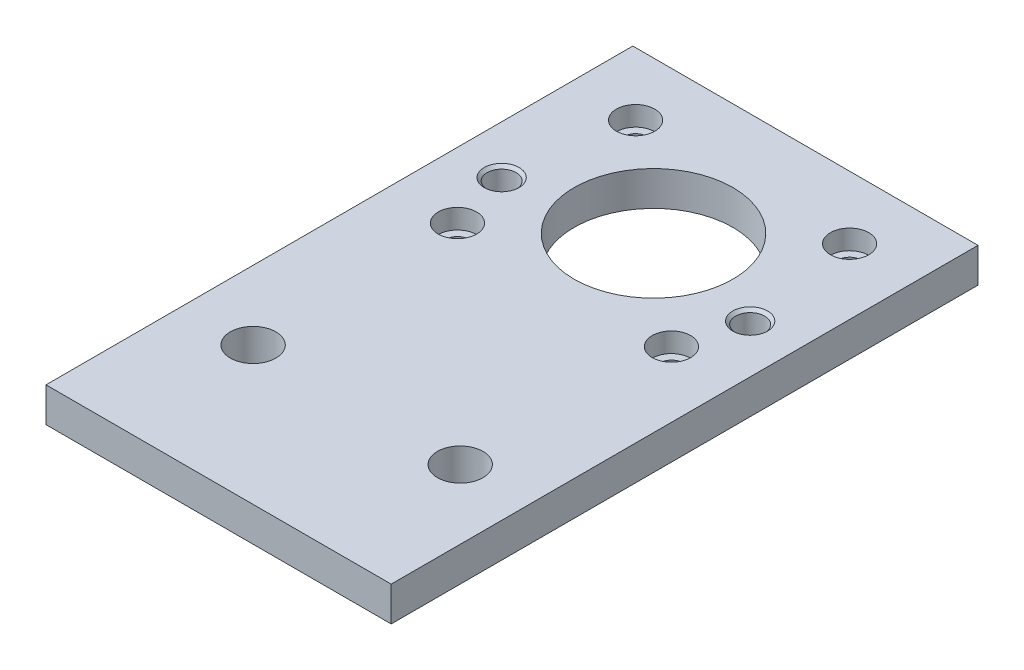
SolidWorks part; units mm, degrees
material "6061-T6 (SS)"
ref_plane "Front Plane" through (0, 0, 0) normal (0, 0, 1) x (1, 0, 0)
ref_plane "Top Plane" through (0, 0, 0) normal (0, 1, 0) x (1, 0, 0)
ref_plane "Right Plane" through (0, 0, 0) normal (1, 0, 0) x (0, 0, -1)
sketch "Sketch1" plane through (0, 0, 0) normal (0, 1, 0) x (1, 0, 0)
  line L0 (5.9071, 63) -> (47.5761, 63) construction
  line L1 (0, 0) -> (50, 0)
  line L2 (0, 0) -> (0, 85)
  line L3 (0, 85) -> (50, 85)
  line L4 (50, 0) -> (50, 85)
  circle A0 centre (25, 63) radius 11.5
  point P7 (25, 85)
  dimension "D4" = 23
  dimension "D1" = 50
  dimension "D2" = 85
  dimension "D3" = 22
extrude "Boss-Extrude1" add sketch "Sketch1" along normal blind 5
hole_wizard "CBORE for #4 Socket Head Cap Screw1" positions "Sketch3" profile "Sketch4" counterbore size "#4" standard "Ansi Inch" end condition through all
sketch "Sketch3" plane through (0, 5, 0) normal (0, 1, 0) x (-1, 0, 0)
  line L7 (-3.7215, -63) -> (-48.1912, -63) construction
  line L9 (-25, -48.4116) -> (-25, -77.5767) construction
  point P0 (-9.5, -75.9033)
  point P76 (-9.5, -50.0967)
  point P78 (-40.5, -50.0967)
  point P79 (-40.5, -75.9033)
  dimension "D1" = 31
sketch "Sketch4" plane through (9.5, 5, -75.9033) normal (1, 0, 0) x (0, 0, 1)
  line L0 (0, 0) -> (0, 5)
  line L1 (0, 5) -> (1.6319, 5)
  line L3 (1.6319, 5) -> (1.6319, 2.8448)
  line L4 (1.6319, 2.8448) -> (2.7788, 2.8448)
  line L5 (2.7788, 2.8448) -> (2.7788, 0)
  line L7 (2.7788, 0) -> (0, 0)
  line L11 (0, -6.35) -> (0, 107.95) construction
  dimension "Thru Hole Dia." = 3.2639
  dimension "Thru Hole Depth" = 5
  dimension "C'Bore Dia." = 5.5575
  dimension "C'Bore Depth" = 2.8448
hole_wizard "M6 Clearance Hole1" positions "Sketch6" profile "Sketch5" hole size "M6" standard "ISO" end condition up to next
sketch "Sketch6" plane through (0, 5, 0) normal (0, 1, 0) x (-1, 0, 0)
  line L0 (-25, 0) -> (-25, -85) construction
  line L1 (0, 0) -> (-50, 0) construction
  line L2 (-50, -85) -> (0, -85) construction
  point P0 (-10, -20)
  point P13 (-40, -20)
  dimension "D1" = 30
  dimension "D2" = 20
sketch "Sketch5" plane through (10, 5, -20) normal (1, 0, 0) x (0, 0, 1)
  line L0 (0, 0) -> (0, 5)
  line L1 (0, 5) -> (3.3, 5)
  line L2 (3.3, 5) -> (3.3, 0)
  line L5 (3.3, 0) -> (0, 0)
  line L11 (0, -6.35) -> (0, 107.95) construction
  dimension "Thru Hole Dia." = 6.6
  dimension "Thru Hole Depth" = 5
ref_axis "Axis1" through (25, 5, -63) along (0, -1, 0)
hole_wizard "M5 Tapped Hole1" positions "Sketch8" profile "Sketch7" tap size "M5" standard "ISO" end condition up to next
sketch "Sketch8" plane through (0, 5, 0) normal (0, 1, 0) x (-1, 0, 0)
  line L0 (-25, -76.9089) -> (-25, -49.0911) construction
  point P0 (-7, -59)
  point P17 (-43, -59)
  dimension "D1" = 18
  dimension "D2" = 4
sketch "Sketch7" plane through (7, 5, -59) normal (1, 0, 0) x (0, 0, 1)
  line L0 (0, 0) -> (0, 5)
  line L1 (0, 5) -> (2.1, 5)
  line L2 (2.1, 5) -> (2.1, 0.425)
  line L3 (2.1, 0.425) -> (2.525, 0)
  line L5 (2.525, 0) -> (0, 0)
  line L6 (-2.1, 0.425) -> (-2.525, 0) construction
  line L11 (0, -6.35) -> (0, 107.95) construction
  dimension "Thru Tap Drill Dia." = 4.2
  dimension "Thru Tap Drill Depth" = 5
  dimension "Near C'Sink Dia." = 5.05
  dimension "Near C'Sink Angle" = 90
cosmetic thread "Hole Thread1"
cosmetic thread "Hole Thread2"
